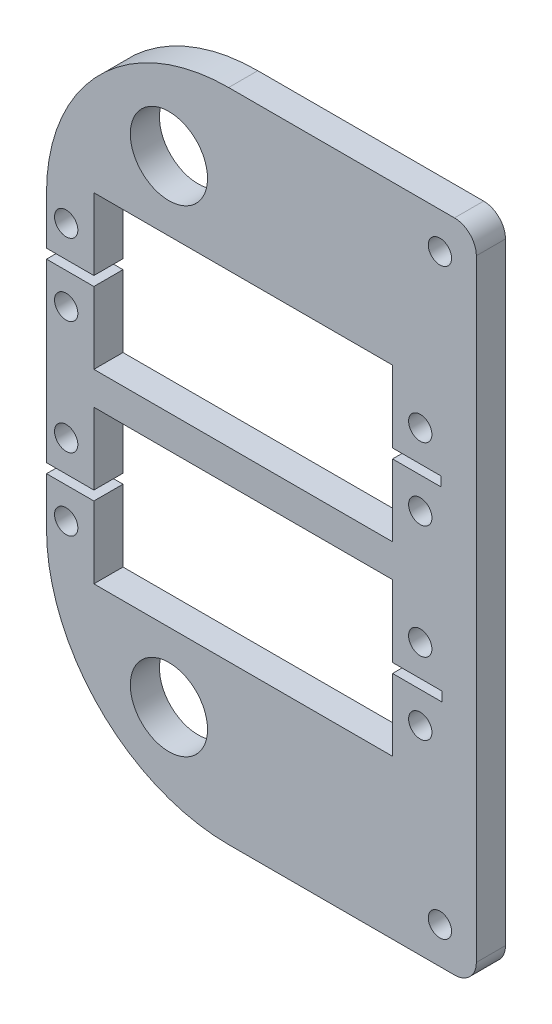
SolidWorks part; units mm, degrees
ref_plane "正面" through (0, 0, 0) normal (0, 0, 1) x (1, 0, 0)
ref_plane "平面" through (0, 0, 0) normal (0, 1, 0) x (1, 0, 0)
ref_plane "右側面" through (0, 0, 0) normal (1, 0, 0) x (0, 0, -1)
sketch "ｽｹｯﾁ1" plane through (0, 0, 0) normal (0, 0, 1) x (1, 0, 0)
  line L0 (-20, 25) -> (-20, 16.25) construction
  line L1 (-27, -32.25) -> (32, -32.25)
  line L2 (-27, -32.25) -> (-27, 57.75)
  line L3 (-27, 57.75) -> (32, 57.75)
  line L4 (32, -32.25) -> (32, 57.75)
  line L5 (-20.5, -10.5) -> (20.5, -10.5)
  line L6 (-20.5, -10.5) -> (-20.5, 10.5)
  line L7 (-20.5, 10.5) -> (20.5, 10.5)
  line L8 (20.5, -10.5) -> (20.5, 10.5)
  line L9 (-20.5, 15) -> (20.5, 15)
  line L10 (-20.5, 15) -> (-20.5, 36)
  line L11 (-20.5, 36) -> (20.5, 36)
  line L12 (20.5, 15) -> (20.5, 36)
  line L13 (-19.5, 15.5) -> (19.5, 15.5) construction
  line L14 (20, 16.25) -> (20, 25) construction
  line L15 (19.5, 35.5) -> (-19.5, 35.5) construction
  line L16 (19.5, 10) -> (-19.5, 10) construction
  line L17 (-19.5, -10) -> (19.5, -10) construction
  line L18 (20, -9.25) -> (20, -0.5) construction
  line L19 (-20, 9.25) -> (-20, 0.5) construction
  line L20 (-27, 7.75) -> (-27, 6.45) construction
  line L21 (27, 17.75) -> (27, 19.05) construction
  line L22 (24.3, 4.95) -> (24.3, 20.55) construction
  line L23 (24.3, 12.75) -> (32, 12.75) construction
  dimension "D1" = 0.5
  dimension "D2" = 0.5
  dimension "D3" = 0.5
  dimension "D4" = 0.5
  dimension "D5" = 0.5
  dimension "D6" = 0.5
  dimension "D7" = 0.5
  dimension "D8" = 0.5
  dimension "D9" = 0
  dimension "D10" = 5
  dimension "D11" = 90
extrude "ﾎﾞｽ - 押し出し1" add sketch "ｽｹｯﾁ1" along normal blind 4
sketch "ｽｹｯﾁ2" plane through (0, 0, 0) normal (0, 0, -1) x (-1, 0, 0)
  line L0 (-20.5, -10.5) -> (-20.5, 10.5) construction
  line L1 (-20.5, 0.65) -> (-27.3, 0.65)
  line L2 (-20.5, 0.65) -> (-20.5, -0.65)
  line L3 (-20.5, -0.65) -> (-27.3, -0.65)
  line L4 (-27.3, 0.65) -> (-27.3, -0.65)
  line L5 (-20.5, 15) -> (-20.5, 36) construction
  line L6 (-20.5, 26.15) -> (-27.15, 26.15)
  line L7 (-20.5, 26.15) -> (-20.5, 24.85)
  line L8 (-20.5, 24.85) -> (-27.15, 24.85)
  line L9 (-27.15, 26.15) -> (-27.15, 24.85)
  line L10 (20.5, 36) -> (20.5, 15) construction
  line L11 (20.5, 24.85) -> (27.15, 24.85)
  line L12 (20.5, 24.85) -> (20.5, 26.15)
  line L13 (20.5, 26.15) -> (27.15, 26.15)
  line L14 (27.15, 24.85) -> (27.15, 26.15)
  line L15 (20.5, 10.5) -> (20.5, -10.5) construction
  line L16 (20.5, -0.65) -> (27.15, -0.65)
  line L17 (20.5, -0.65) -> (20.5, 0.65)
  line L18 (20.5, 0.65) -> (27.15, 0.65)
  line L19 (27.15, -0.65) -> (27.15, 0.65)
  line L20 (-27, 0.5) -> (-27, -0.5) construction
  line L21 (-27, 0.5) -> (-20, 0.5) construction
  line L22 (-27, -0.5) -> (-20, -0.5) construction
  line L23 (-27, 26) -> (-27, 25) construction
  line L24 (-27, 25) -> (-20, 25) construction
  line L25 (-27, 26) -> (-20, 26) construction
  line L26 (27, -0.5) -> (27, 0.5) construction
  line L27 (27, 0.5) -> (20, 0.5) construction
  line L28 (27, -0.5) -> (20, -0.5) construction
  line L29 (27, 25) -> (27, 26) construction
  line L30 (27, 26) -> (20, 26) construction
  line L31 (27, 25) -> (20, 25) construction
  circle A0 centre (-24.3, -4.95) radius 1.6
  circle A1 centre (-24.3, 4.95) radius 1.6
  circle A2 centre (-24.3, 20.55) radius 1.6
  circle A3 centre (-24.3, 30.45) radius 1.6
  circle A4 centre (24.3, 30.45) radius 1.6
  circle A5 centre (24.3, 20.55) radius 1.6
  circle A6 centre (24.3, 4.95) radius 1.6
  circle A7 centre (24.3, -4.95) radius 1.6
  dimension "D13" = 3.2
  dimension "D1" = 0.3
  dimension "D2" = 0.15
  dimension "D3" = 0.15
  dimension "D4" = 0.15
  dimension "D5" = 0.15
  dimension "D6" = 0.15
  dimension "D7" = 0.15
  dimension "D8" = 0.15
  dimension "D9" = 0.15
  dimension "D10" = 0.15
  dimension "D11" = 0.15
  dimension "D12" = 0.15
extrude "ｶｯﾄ - 押し出し1" cut sketch "ｽｹｯﾁ2" against normal blind 4
sketch "ｽｹｯﾁ3" plane through (0, 0, 4) normal (0, 0, 1) x (1, 0, 0)
  circle A0 centre (-10.2, 45.5) radius 5.3
  circle A1 centre (-10.2, -20) radius 5.3
  circle A2 centre (-10.2, 25.5) radius 1.5 construction
  circle A3 centre (-10.2, 0) radius 1.25 construction
  circle A4 centre (-10.2, 0) radius 2.75 construction
  dimension "D1" = 10.6
  dimension "D2" = 10.6
  dimension "D3" = 0
  dimension "D4" = 0
  dimension "D5" = 20
  dimension "D6" = 20
extrude "ｶｯﾄ - 押し出し2" cut sketch "ｽｹｯﾁ3" against normal blind 4
fillet "ﾌｨﾚｯﾄ1" radius 25 2 edges at (-27, -32.25, 2) (-27, 57.75, 2)
fillet "ﾌｨﾚｯﾄ2" radius 3 2 edges at (32, -32.25, 2) (32, 57.75, 2)
sketch "ｽｹｯﾁ4" plane through (0, 0, 4) normal (0, 0, 1) x (1, 0, 0)
  line L0 (27, -27.25) -> (27, 52.75) construction
  line L1 (32, -29.25) -> (32, 54.75) construction
  line L2 (-2, -32.25) -> (29, -32.25) construction
  line L3 (29, 57.75) -> (-2, 57.75) construction
  circle A0 centre (27, 52.75) radius 1.6
  circle A1 centre (27, -27.25) radius 1.6
  dimension "D2" = 5
  dimension "D3" = 5
  dimension "D4" = 3.2
  dimension "D1" = 5
extrude "ｶｯﾄ - 押し出し3" cut sketch "ｽｹｯﾁ4" against normal blind 10
